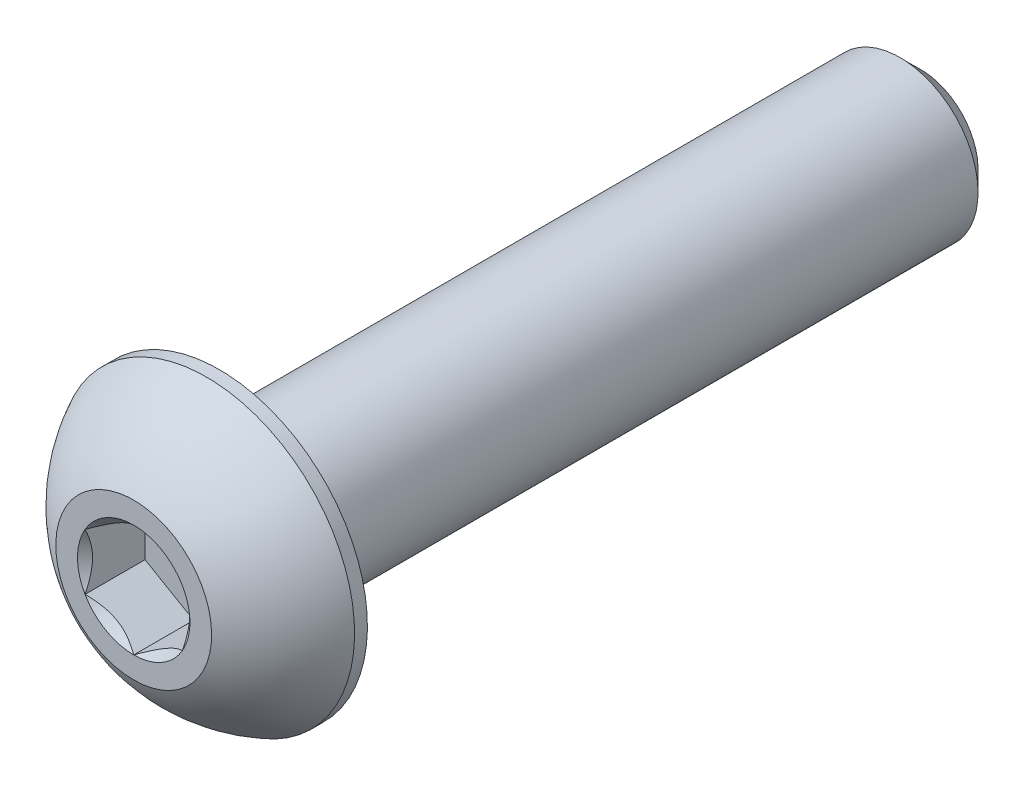
SolidWorks part; units mm, degrees
ref_plane "Front" through (0, 0, 0) normal (0, 0, 1) x (1, 0, 0)
ref_plane "Top" through (0, 0, 0) normal (0, 1, 0) x (1, 0, 0)
ref_plane "Right" through (0, 0, 0) normal (1, 0, 0) x (0, 0, -1)
sketch "Sketch1" plane through (0, 0, 0) normal (1, 0, 0) x (0, 0, -1)
  line L2 (-9, 2) -> (9, 2)
  line L3 (9, 2) -> (9, 0)
  line L4 (9, 0) -> (-9, 0)
  line L6 (-9.33, 3.8) -> (-9, 3.8) construction
  line L7 (9, 2) -> (9, -2) construction
  line L8 (-11.2, 0) -> (-9, 0) construction
  line L9 (-9, 3.8) -> (-9, -3.8) construction
  line L11 (-9, 2) -> (-9, 0)
  line L13 (-11.2, 1.25) -> (-11.2, -1.25) construction
  line L14 (-11.2, 1.25) -> (-11.2, 2) construction
  line L15 (8.9563, 2.0758) -> (9.3063, 1.4696) construction
  line L16 (9.3063, 1.4696) -> (9.6563, 2.0758) construction
  line L17 (9.6563, 2.0758) -> (8.9563, 2.0758) construction
  line L18 (9, 2) -> (9.6125, 2) construction
  line L19 (9.3063, 2.0758) -> (9.3063, 2) construction
  line L20 (9.3063, 2) -> (9.3063, 1.5453) construction
  line L21 (9.3063, 1.5453) -> (9.3063, 1.4696) construction
  line L22 (9.2625, 1.5453) -> (9.35, 1.5453)
  line L23 (8.9781, 2.0379) -> (9.6344, 2.0379)
  line L24 (9.35, 1.5453) -> (9.6344, 2.0379)
  line L25 (9.2625, 1.5453) -> (8.9781, 2.0379)
  line L26 (8.475, 2) -> (9, 1.475)
  arc A3 (-11.2, 2) -> (-9.33, 3.8) centre (-7.4736, 0) cw construction
  point P29 (9.3063, 2.0379)
  point P30 (7.25, -2)
  point P33 (0, 0)
  dimension "Thread Size" = 4
  dimension "D1" = 0.33
  dimension "Head Height" = 2.2
  dimension "Head Diameter" = 7.6
  dimension "Length" = 18
  dimension "Drive Size" = 2.5
  dimension "Thread Pitch" = 0.7
  dimension "D3" = 0.0875
  dimension "D2" = 0.525
  dimension "D4" = 45
  dimension "D5" = 1.75
sketch "Sketch10" plane through (0, 0, 0) normal (1, 0, 0) x (0, 0, -1)
  line L0 (8.475, 2) -> (9, 1.475) construction
  line L1 (8.475, 2) -> (9, 1.475)
  line L4 (9, 2) -> (-9, 2)
  line L5 (9, 0) -> (9, 2)
  line L6 (-9, 0) -> (9, 0)
  line L7 (-9, 2) -> (-9, 0)
  line L8 (8.475, 2) -> (-9, 2)
  line L9 (9, 0) -> (9, 1.475)
  line L10 (-9, 0) -> (9, 0)
  line L11 (-9, 2) -> (-9, 0)
  dimension "D1" = 0
revolve "Revolve3" add sketch "Sketch10" angle 360 about L8
sketch "Sketch7" plane through (0, 0, 0) normal (1, 0, 0) x (0, 0, -1)
  line L6 (-9.33, 3.8) -> (-9, 3.8) construction
  line L8 (-11.2, 0) -> (-9, 0) construction
  line L11 (-9, 3.8) -> (-9, -3.8) construction
  line L12 (-9.33, 3.8) -> (-9, 3.8)
  line L13 (-11.2, 0) -> (-9, 0)
  line L14 (-11.2, 1.25) -> (-11.2, -1.25) construction
  line L15 (-9, 3.8) -> (-9, 0)
  line L16 (-11.2, 2) -> (-11.2, 0)
  arc A2 (-9.33, 3.8) -> (-11.2, 2) centre (-7.4736, 0) ccw construction
  arc A3 (-9.33, 3.8) -> (-11.2, 2) centre (-7.4736, 0) ccw
revolve "Revolve2" add sketch "Sketch7" angle 360 mid plane about L13
sketch "Sketch5" plane through (0, 0, 11.2) normal (0, 0, 1) x (1, 0, 0)
  line L1 (1.25, -0.7217) -> (1.25, 0.7217)
  line L2 (1.25, 0.7217) -> (0, 1.4434)
  line L3 (0, 1.4434) -> (-1.25, 0.7217)
  line L4 (-1.25, 0.7217) -> (-1.25, -0.7217)
  line L5 (-1.25, -0.7217) -> (0, -1.4434)
  line L6 (0, -1.4434) -> (1.25, -0.7217)
  circle A0 centre (0, 0) radius 1.25 construction
extrude "Cut-Extrude2" cut sketch "Sketch5" against normal blind 1.54
sketch "Sketch6" plane through (0, 0, 11.2) normal (0, 0, 1) x (1, 0, 0)
  circle A0 centre (0, 0) radius 1.4434
extrude "Cut-Extrude3" cut sketch "Sketch6" against normal blind 1.54 draft 45
sketch "Sketch9" plane through (0, 0, 9) normal (0, 0, -1) x (-1, 0, 0)
  circle A0 centre (0, 0) radius 2 construction
  circle A4 centre (0, 0) radius 2
split "Split1" [suppressed] bodies to split 113
sketch "Sketch11" plane through (0, 0, -9) normal (0, 0, -1) x (-1, 0, 0)
  circle A0 centre (0, 0) radius 2 construction
  circle A1 centre (0, 0) radius 2
curve "Helix/Spiral1" [suppressed] pitch 0.7 height 20.2 turns 28.8571
sketch "Sketch12" plane through (0, 0, 0) normal (1, 0, 0) x (0, 0, -1)
  line L0 (9.2625, 1.5453) -> (9.35, 1.5453) construction
  line L1 (9.35, 1.5453) -> (9.6344, 2.0379) construction
  line L2 (8.9781, 2.0379) -> (9.6344, 2.0379) construction
  line L3 (9.2625, 1.5453) -> (8.9781, 2.0379) construction
  line L4 (9.2625, 1.5453) -> (9.35, 1.5453)
  line L5 (9.35, 1.5453) -> (9.6344, 2.0379)
  line L6 (8.9781, 2.0379) -> (9.6344, 2.0379)
  line L7 (9.2625, 1.5453) -> (8.9781, 2.0379)
sweep "Cut-Sweep2" [suppressed] cut profiles "Sketch12" path "Helix/Spiral1"
extrude "Boss-Extrude1" [suppressed] add sketch "Sketch9" along normal blind 10 draft 45
equation "\"D1@Cut-Extrude2\" = \"Head Height@Sketch1\" * .7"
equation "\"D1@Sketch1\" = \"Head Height@Sketch1\" * .15"
equation "\"D1@Cut-Extrude3\" = \"D1@Cut-Extrude2\""
equation "\"D3@Sketch1\" = \"Thread Pitch@Sketch1\" / 8"
equation "\"D2@Sketch1\" = \"Thread Pitch@Sketch1\" * 0.75"
equation "\"D3@Helix/Spiral1\" = \"Length@Sketch1\" + \"Head Height@Sketch1\""
equation "\"D4@Helix/Spiral1\" = \"Thread Pitch@Sketch1\""
equation "\"D5@Sketch1\" = \"Thread Pitch@Sketch1\" * 2.5"
